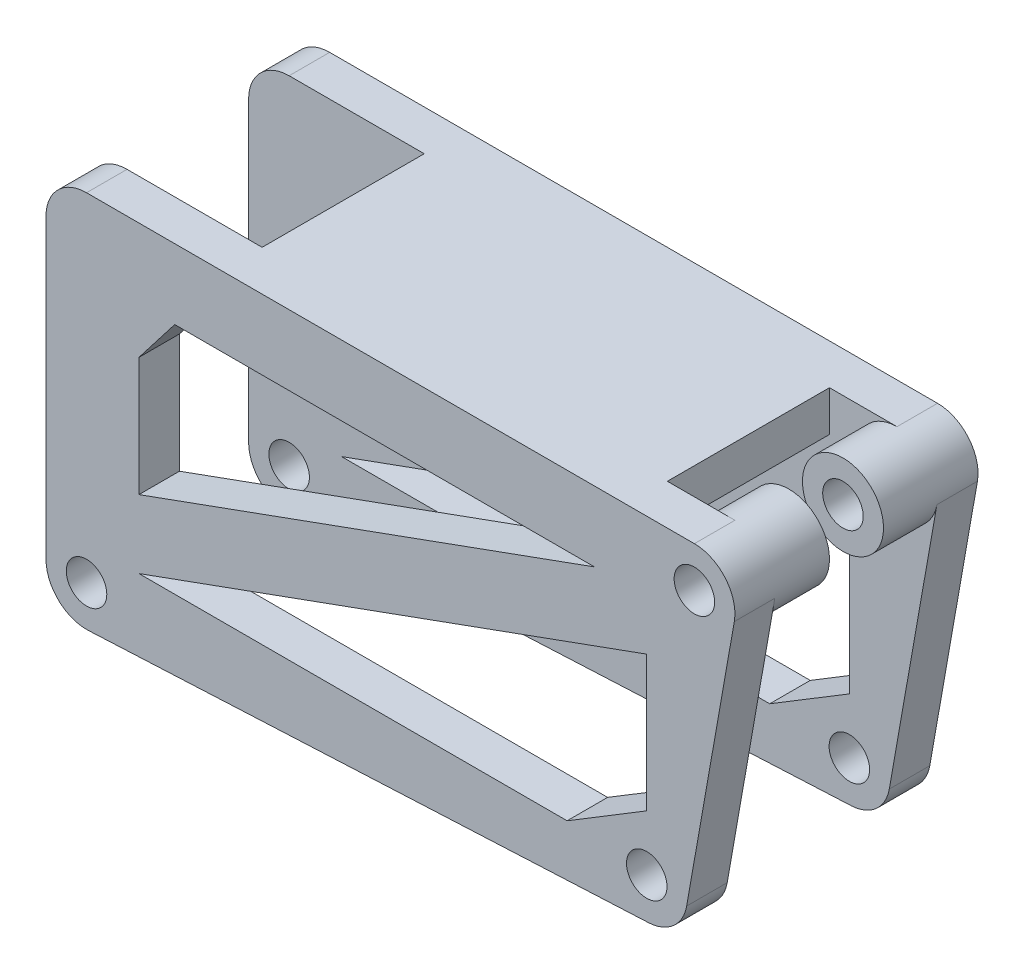
SolidWorks part; units mm, degrees
ref_plane "Front Plane" through (0, 0, 0) normal (0, 0, 1) x (1, 0, 0)
ref_plane "Top Plane" through (0, 0, 0) normal (0, 1, 0) x (1, 0, 0)
ref_plane "Right Plane" through (0, 0, 0) normal (1, 0, 0) x (0, 0, -1)
sketch "Sketch1" plane through (0, 0, 0) normal (0, 0, 1) x (1, 0, 0)
  line L0 (0, 3) -> (45, 3)
  line L1 (47.9544, -0.5209) -> (44.4279, -20.5209)
  line L2 (41.618, -22.9965) -> (0.1445, -24.9965)
  line L3 (-3, -22) -> (-3, 0)
  line L8 (3.8811, -14.414) -> (3.8811, -5.6136)
  line L9 (3.8811, -5.6136) -> (6.529, -2.1869)
  line L10 (6.529, -2.1869) -> (37.603, -2.1869)
  line L11 (37.603, -2.1869) -> (3.8811, -14.414)
  line L12 (3.8811, -19.4762) -> (41.4735, -5.8457)
  line L13 (41.4735, -5.8457) -> (41.4735, -15.8937)
  line L14 (41.4735, -15.8937) -> (35.5781, -19.4762)
  line L15 (35.5781, -19.4762) -> (3.8811, -19.4762)
  circle A0 centre (45, 0) radius 1.5
  circle A1 centre (41.4735, -20) radius 1.5
  arc A3 (45, 3) -> (47.9544, -0.5209) centre (45, 0) cw
  arc A4 (44.4279, -20.5209) -> (41.618, -22.9965) centre (41.4735, -20) cw
  arc A5 (-3, -22) -> (0.1445, -24.9965) centre (0, -22) ccw
  circle A6 centre (0, -22) radius 1.5
  arc A7 (-3, 0) -> (0, 3) centre (0, 0) cw
  dimension "D1" = 3
  dimension "D6" = 3
  dimension "D9" = 3
  dimension "D2" = 3
  dimension "D3" = 20
  dimension "D4" = 80
  dimension "D5" = 3
  dimension "D10" = 25
  dimension "D11" = 45
extrude "Boss-Extrude1" add sketch "Sketch1" along normal blind 3
pattern_linear "LPattern1" count 2 spacing 15 along (0, 0, 1) of "Boss-Extrude1"
sketch "Sketch2" plane through (0, 0, 3) normal (0, 0, 1) x (1, 0, 0)
  circle A0 centre (45, 0) radius 3
  circle A2 centre (45, 0) radius 1.5 construction
  circle A3 centre (45, 0) radius 1.5
  dimension "D1" = 1.5
extrude "Boss-Extrude2" add sketch "Sketch2" along normal blind 4
pattern_linear "LPattern2" count 2 spacing 8 along (0, 0, 1) of "Boss-Extrude2"
sketch "Sketch3" plane through (0, 0, 3) normal (0, 0, 1) x (1, 0, 0)
  line L0 (45, 3) -> (0, 3) construction
  line L1 (40, 3) -> (10, 3)
  line L2 (40, 3) -> (40, 0)
  line L3 (40, 0) -> (10, 0)
  line L4 (10, 3) -> (10, 0)
  dimension "D1" = 3
  dimension "D2" = 30
  dimension "D3" = 5
extrude "Boss-Extrude3" add sketch "Sketch3" along normal up to next
